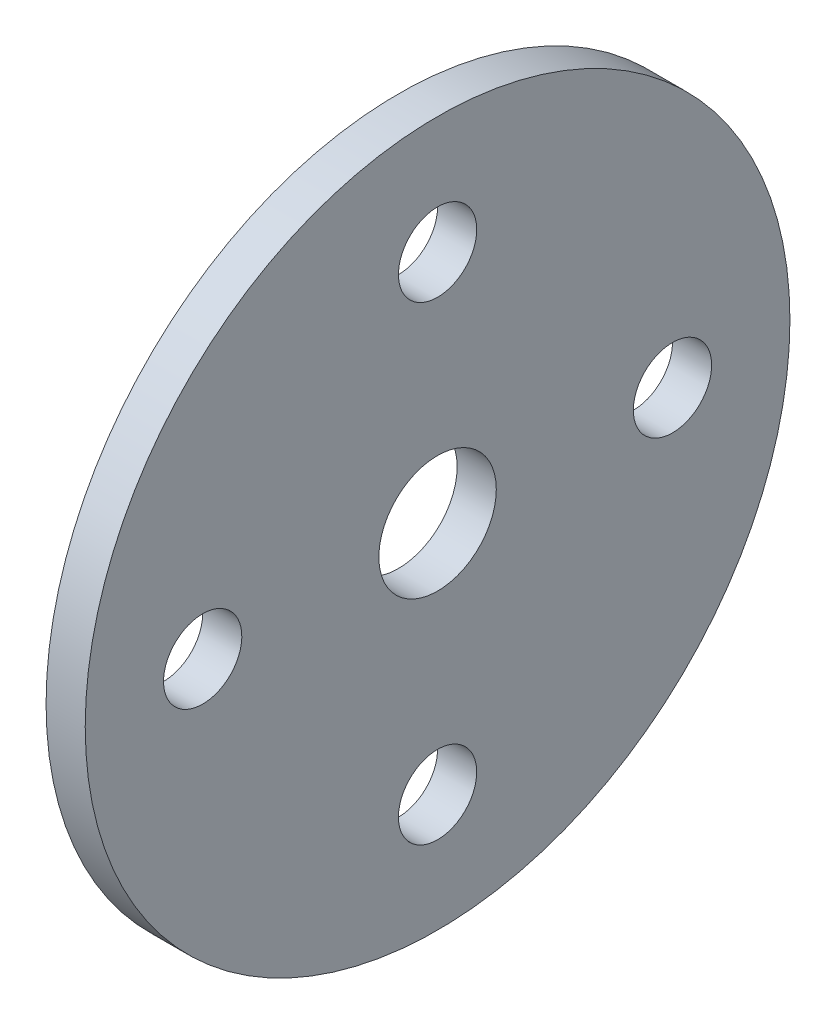
SolidWorks part; units mm, degrees
material "1023 Carbon Steel Sheet (SS)"
ref_plane "Front Plane" through (0, 0, 0) normal (0, 0, 1) x (1, 0, 0)
ref_plane "Top Plane" through (0, 0, 0) normal (0, 1, 0) x (1, 0, 0)
ref_plane "Right Plane" through (0, 0, 0) normal (1, 0, 0) x (0, 0, -1)
sketch "Sketch1" plane through (0, 0, 0) normal (1, 0, 0) x (0, 0, -1)
  circle A0 centre (0, 0) radius 28.575
  circle A1 centre (0, 0) radius 4.7625
  circle A2 centre (0, 0) radius 11.1125 construction
  dimension "D1" = 9.525
  dimension "OD" = 57.15
  dimension "D2" = 22.225
extrude "Boss-Extrude1" add sketch "Sketch1" along normal blind 3.175
sketch "Sketch2" plane through (0, 0, 0) normal (1, 0, 0) x (0, 0, -1)
  line L0 (-28.575, 0) -> (28.575, 0) construction
  circle A0 centre (0, 19.05) radius 3.175
  circle A1 centre (0, 0) radius 28.575 construction
  point P12 (0, 0)
  dimension "D2" = 6.35
  dimension "D1" = 19.05
extrude "Cut-Extrude1" cut sketch "Sketch2" along normal through all
pattern_circular "CirPattern1" count 4 over 360 about axis through (3.175, 0, 0) along (1, 0, 0) of "Cut-Extrude1"
